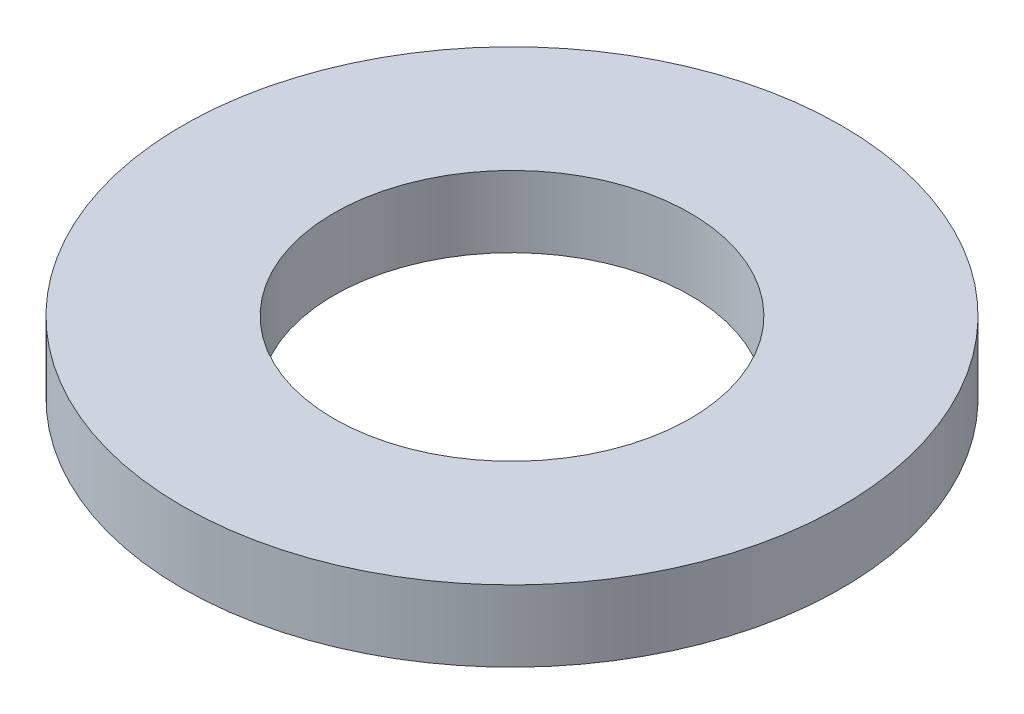
SolidWorks part; units mm, degrees
ref_plane "Front Plane" through (0, 0, 0) normal (0, 0, 1) x (1, 0, 0)
ref_plane "Top Plane" through (0, 0, 0) normal (0, 1, 0) x (1, 0, 0)
ref_plane "Right Plane" through (0, 0, 0) normal (1, 0, 0) x (0, 0, -1)
sketch "Sketch1" plane through (0, 0, 0) normal (0, 1, 0) x (1, 0, 0)
  circle A0 centre (0, 0) radius 92.5
  dimension "FLANGE_OD" = 185
extrude "Boss-Extrude1" add sketch "Sketch1" along normal blind 20
sketch "Sketch2" plane through (0, 0, 0) normal (0, 1, 0) x (1, 0, 0)
  circle A0 centre (0, 0) radius 50
  dimension "BORE_D" = 100
extrude "Cut-Extrude1" cut sketch "Sketch2" along normal through all
sketch "Sketch3" plane through (0, 20, 0) normal (0, 1, 0) x (1, 0, 0)
  circle A0 centre (0, 0) radius 40.5628 construction
  circle A1 centre (-40.5628, 0) radius 4.3693
  dimension "BOLT_D" = 8.7386
  dimension "BOLT_PCD" = 81.1255
extrude "Cut-Extrude2" cut sketch "Sketch3" against normal blind 13.7093 rebuild error yes
pattern_circular "CirPattern1" count 8 over 360 rebuild error yes
